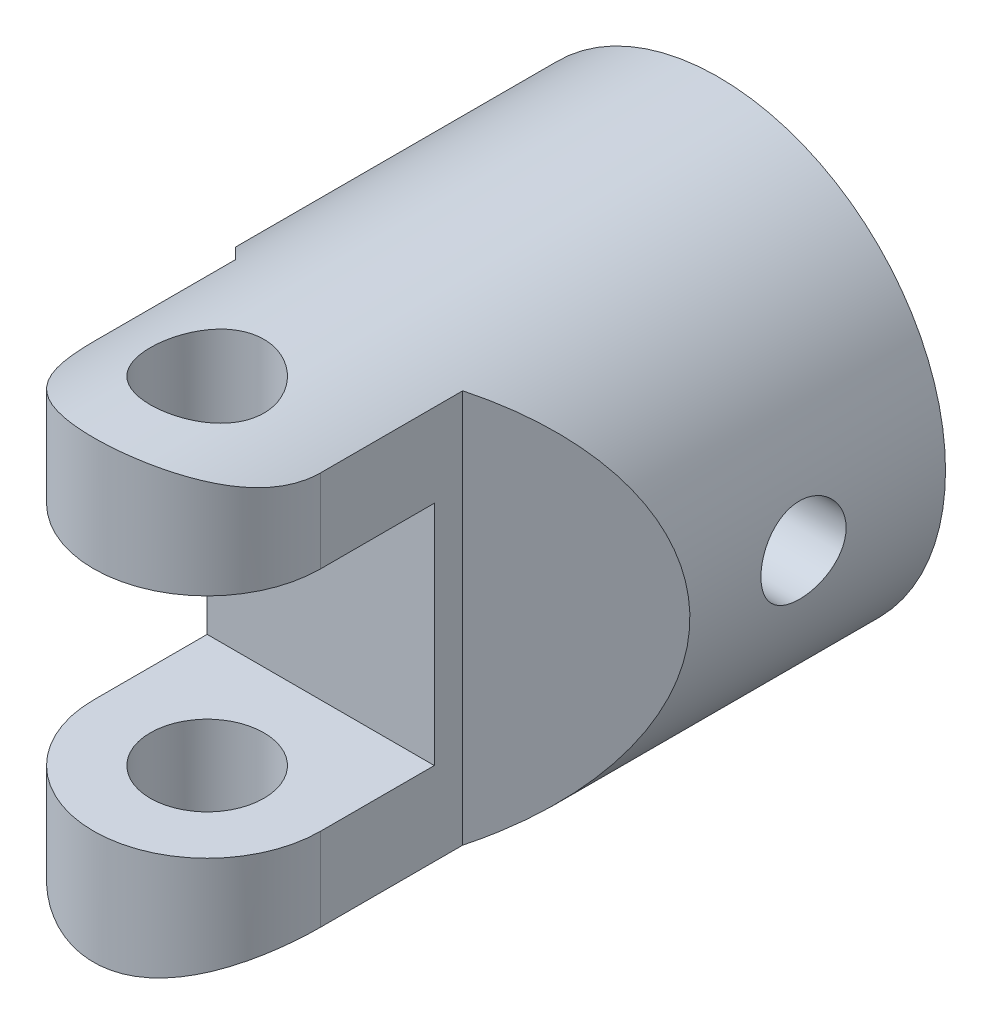
SolidWorks part; units mm, degrees
ref_plane "前视基准面" through (0, 0, 0) normal (0, 0, 1) x (1, 0, 0)
ref_plane "上视基准面" through (0, 0, 0) normal (0, 1, 0) x (1, 0, 0)
ref_plane "右视基准面" through (0, 0, 0) normal (1, 0, 0) x (0, 0, -1)
sketch "草图1" plane through (0, 0, 0) normal (0, 0, 1) x (1, 0, 0)
  circle A0 centre (0, 0) radius 8
  dimension "D1" = 16
extrude "拉伸1" add sketch "草图1" along normal blind 22
sketch "草图2" plane through (0, 0, 0) normal (0, 1, 0) x (1, 0, 0)
  line L1 (8, -9) -> (4, -13)
  line L3 (-8, -9) -> (-4, -13)
  line L4 (-8, -22) -> (8, -22) construction
  line L5 (8, -22) -> (8, 0) construction
  line L7 (-4, -18) -> (-4, -13)
  line L8 (8, -22) -> (8, -9)
  line L9 (4, -13) -> (4, -18)
  line L10 (-8, -22) -> (1.4832, -24.7002)
  line L11 (1.4832, -24.7002) -> (8, -22)
  line L12 (-8, 0) -> (-8, -22) construction
  line L13 (-8, -9) -> (-8, -22)
  arc A0 (-4, -18) -> (4, -18) centre (0, -18) ccw
  dimension "D1" = 8
extrude "切除-拉伸1" cut sketch "草图2" against normal through all and the other way through all
sketch "草图3" plane through (0, 0, 0) normal (0, 1, 0) x (1, 0, 0)
  circle A0 centre (0, -18) radius 2
  dimension "D1" = 4
extrude "切除-拉伸2" cut sketch "草图3" against normal blind 26 and the other way blind 26
sketch "草图4" plane through (0, 0, 0) normal (1, 0, 0) x (0, 0, -1)
  line L0 (-22, 8) -> (-22, -8) construction
  line L1 (-22, 4) -> (-14, 4)
  line L2 (-22, 4) -> (-22, -4)
  line L3 (-22, -4) -> (-14, -4)
  line L4 (-14, 4) -> (-14, -4)
  line L5 (0, 8) -> (-16, 8) construction
  dimension "D1" = 8
  dimension "D2" = 8
  dimension "D3" = 4
extrude "切除-拉伸3" cut sketch "草图4" against normal blind 26 and the other way blind 26
sketch "草图5" plane through (0, 0, 0) normal (0, 0, -1) x (-1, 0, 0)
  circle A0 centre (0, 0) radius 4
  dimension "D1" = 8
extrude "切除-拉伸4" cut sketch "草图5" against normal blind 9
sketch "草图6" plane through (0, 0, 0) normal (1, 0, 0) x (0, 0, -1)
  line L0 (-1009, 0) -> (48991, 0) construction
  line L1 (-9, -4) -> (-9, 4) construction
  line L2 (0, -8) -> (0, 8) construction
  circle A0 centre (-5, 0) radius 1.5
  point P5 (-9, 0)
  dimension "D1" = 3
  dimension "D2" = 5
extrude "切除-拉伸5" cut sketch "草图6" against normal through all and the other way through all
